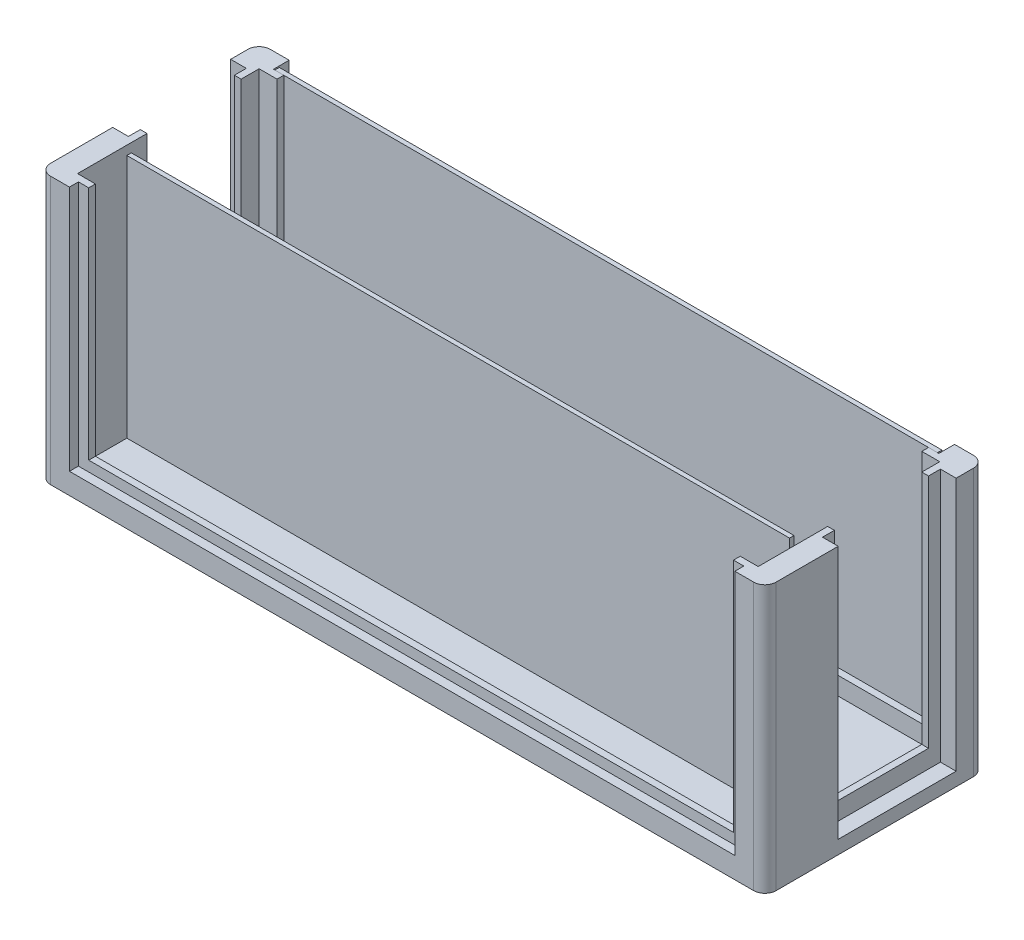
SolidWorks part; units mm, degrees
note: The reader was unsure of these and kept them because the rebuilt part matched: shared geometry of "Sketch2<3>", "Sketch3<3>", "Sketch14<2>".
other "Window_Left"
other "Window_Right"
other "Window_Back"
other "Window_Front"
other "Body"
ref_plane "Front Plane" through (0, 0, 0) normal (0, 0, 1) x (1, 0, 0)
ref_plane "Top Plane" through (0, 0, 0) normal (0, 1, 0) x (1, 0, 0)
ref_plane "Right Plane" through (0, 0, 0) normal (1, 0, 0) x (0, 0, -1)
sketch "Sketch1" plane through (0, 0, 0) normal (0, 0, 1) x (1, 0, 0)
  line L1 (0, 0) -> (157.8, 0)
  line L2 (0, 0) -> (0, 59.6)
  line L3 (0, 59.6) -> (157.8, 59.6)
  line L4 (157.8, 0) -> (157.8, 59.6)
  dimension "D1" = 59.6
  dimension "D2" = 157.8
extrude "Boss-Extrude1" add sketch "Sketch1" along normal blind 35 contours L3 L4 L1 L2
shell "Shell1" thickness 3
sketch "Sketch2" plane through (0, 0, 35) normal (0, 0, 1) x (1, 0, 0)
  line L0 (0, 59.6) -> (157.8, 59.6) construction
  line L1 (5, 59.6) -> (152.8, 59.6)
  line L2 (5, 59.6) -> (5, 5)
  line L3 (5, 5) -> (152.8, 5)
  line L4 (152.8, 59.6) -> (152.8, 5)
  line L5 (0, 0) -> (0, 59.6) construction
  line L6 (157.8, 0) -> (157.8, 59.6) construction
  line L7 (0, 0) -> (157.8, 0) construction
  line L8 (7, 57.6) -> (7, 7)
  line L9 (7, 7) -> (150.8, 7)
  line L10 (150.8, 57.6) -> (150.8, 7)
  line L11 (7, 57.6) -> (150.8, 57.6)
  line L13 (7, 57.6) -> (150.8, 57.6)
  line L14 (7, 57.6) -> (7, 59.6)
  line L15 (7, 59.6) -> (150.8, 59.6)
  line L16 (150.8, 57.6) -> (150.8, 59.6)
  dimension "D1" = 5
  dimension "D2" = 5
  dimension "D3" = 5
  dimension "D4" = 2
extrude "Cut-Extrude1" cut sketch "Sketch2" against normal through all contours L11 L8 L9 L10 | L11 L16 L1 L14
extrude "Cut-Extrude2" cut sketch "Sketch2<3>" against normal blind 1.5 contours L3 L4 L1 L2
sketch "Sketch2<3>" plane through (0, 0, 35) normal (0, 0, 1) x (1, 0, 0) same geometry as "Sketch2"
ref_plane "Plane1" through (0, 0, 17.5) normal (0, 0, 1) x (1, 0, 0)
mirror "Mirror1" about plane through (0, 0, 17.5) normal (0, 0, 1) of "Cut-Extrude2"
sketch "Sketch3" plane through (157.8, 0, 0) normal (1, 0, 0) x (0, 0, -1)
  line L0 (-35, 59.6) -> (0, 59.6) construction
  line L1 (-30, 59.6) -> (-5, 59.6)
  line L2 (-30, 59.6) -> (-30, 5)
  line L3 (-30, 5) -> (-5, 5)
  line L4 (-5, 59.6) -> (-5, 5)
  line L5 (-35, 0) -> (-35, 59.6) construction
  line L6 (0, 0) -> (0, 59.6) construction
  line L7 (-35, 0) -> (0, 0) construction
  line L9 (-28, 59.6) -> (-7, 59.6)
  line L10 (-28, 59.6) -> (-28, 7)
  line L11 (-28, 7) -> (-7, 7)
  line L12 (-7, 59.6) -> (-7, 7)
  dimension "D1" = 5
  dimension "D2" = 5
  dimension "D3" = 5
  dimension "D4" = 2
  dimension "D5" = 2
  dimension "D6" = 2
ref_plane "Plane2" through (78.9, 0, 0) normal (1, 0, 0) x (0, 0, -1)
extrude "Cut-Extrude3" cut sketch "Sketch3" against normal through all contours L12 L1 L10 L11
extrude "Cut-Extrude4" cut sketch "Sketch3<3>" against normal blind 1.5 contours L1 L4 L3 L2
sketch "Sketch3<3>" plane through (157.8, 0, 0) normal (1, 0, 0) x (0, 0, -1) same geometry as "Sketch3"
mirror "Mirror2" about plane through (78.9, 0, 0) normal (1, 0, 0) of "Cut-Extrude4"
sketch "Sketch4" plane through (0, 0, 33.5) normal (0, 0, 1) x (1, 0, 0)
  line L1 (5, 5) -> (152.8, 5)
  line L2 (5, 5) -> (5, 59.6)
  line L3 (5, 59.6) -> (152.8, 59.6)
  line L4 (152.8, 5) -> (152.8, 59.6)
extrude "Boss-Extrude2" add sketch "Sketch4" along normal blind 1 separate body
mirror "Mirror3" about plane through (0, 0, 17.5) normal (0, 0, 1) of bodies 108
sketch "Sketch5" plane through (156.3, 0, 0) normal (1, 0, 0) x (0, 0, -1)
  line L1 (-30, 5) -> (-5, 5)
  line L2 (-30, 5) -> (-30, 59.6)
  line L3 (-30, 59.6) -> (-5, 59.6)
  line L4 (-5, 5) -> (-5, 59.6)
extrude "Boss-Extrude3" add sketch "Sketch5" along normal blind 1 separate body contours L3 L4 L1 L2
mirror "Mirror4" about plane through (78.9, 0, 0) normal (1, 0, 0) of bodies 110
delete or keep bodies "Body-Delete/Keep 1" type delete bodies bodies 110 111
sketch "Sketch6" plane through (157.8, 0, 0) normal (1, 0, 0) x (0, 0, -1)
  line L0 (-35, 59.6) -> (-30, 59.6) construction
  line L1 (-30.15, 59.6) -> (-4.85, 59.6)
  line L2 (-30.15, 59.6) -> (-30.15, 3)
  line L3 (-30.15, 3) -> (-4.85, 3)
  line L4 (-4.85, 59.6) -> (-4.85, 3)
  line L5 (-35, 0) -> (-35, 59.6) construction
  dimension "D1" = 25.3
  dimension "D2" = 4.85
  dimension "D3" = 56.6
extrude "Cut-Extrude5" cut sketch "Sketch6" against normal blind 1.5
mirror "Mirror5" about plane through (78.9, 0, 0) normal (1, 0, 0) of "Cut-Extrude5"
sketch "Sketch7" plane through (157.8, 0, 0) normal (1, 0, 0) x (0, 0, -1)
  line L1 (-30.65, 59.6) -> (-4.35, 59.6)
  line L2 (-30.65, 59.6) -> (-30.65, 3)
  line L3 (-30.65, 3) -> (-4.35, 3)
  line L4 (-4.35, 59.6) -> (-4.35, 3)
  line L5 (-30.15, 3) -> (-4.85, 3) construction
  line L7 (-30.15, 59.6) -> (-30.15, 3) construction
  line L8 (-4.85, 3) -> (-4.85, 59.6) construction
  dimension "D1" = 0.5
  dimension "D2" = 0.5
extrude "Cut-Extrude6" cut sketch "Sketch7" against normal up to surface (1.5 mm away) up to face at (156.3, 32.3, 17.5)
sketch "Sketch8" plane through (0, 0, 0) normal (-1, 0, 0) x (0, 0, 1)
  line L0 (30.65, 3) -> (4.35, 3) construction
  line L1 (4.35, 59.6) -> (4.35, 3) construction
  line L2 (30.65, 59.6) -> (4.35, 59.6) construction
  line L3 (30.65, 59.6) -> (30.65, 3) construction
  line L4 (30.65, 3) -> (4.35, 3)
  line L5 (4.35, 59.6) -> (4.35, 3)
  line L6 (30.65, 59.6) -> (4.35, 59.6)
  line L7 (30.65, 59.6) -> (30.65, 3)
extrude "Cut-Extrude7" cut sketch "Sketch8" against normal up to surface (1.5 mm away) up to face at (1.5, 32.3, 17.5)
sketch "Sketch9" plane through (0, 0, 0) normal (0, 0, -1) x (-1, 0, 0)
  line L8 (0, 59.6) -> (-5, 59.6)
  line L9 (-5, 59.6) -> (-5, 5)
  line L10 (-5, 5) -> (-152.8, 5)
  line L11 (-152.8, 5) -> (-152.8, 59.6)
  line L12 (-152.8, 59.6) -> (-157.8, 59.6)
  line L13 (-157.8, 59.6) -> (-157.8, 0)
  line L14 (-157.8, 0) -> (0, 0)
  line L15 (0, 0) -> (0, 59.6)
  line L16 (0, 59.6) -> (-5, 59.6)
  line L17 (-5, 59.6) -> (-5, 5)
  line L18 (-5, 5) -> (-152.8, 5)
  line L19 (-152.8, 5) -> (-152.8, 59.6)
  line L20 (-152.8, 59.6) -> (-157.8, 59.6)
  line L21 (-157.8, 59.6) -> (-157.8, 0)
  line L22 (-157.8, 0) -> (0, 0)
  line L23 (0, 0) -> (0, 59.6)
  dimension "D1" = 0
extrude "Boss-Extrude4" add sketch "Sketch9" along normal blind 2
sketch "Sketch10" plane through (0, 0, 35) normal (0, 0, 1) x (1, 0, 0)
  line L8 (152.8, 5) -> (5, 5)
  line L9 (5, 5) -> (5, 59.6)
  line L10 (5, 59.6) -> (0, 59.6)
  line L11 (0, 59.6) -> (0, 0)
  line L12 (0, 0) -> (157.8, 0)
  line L13 (157.8, 0) -> (157.8, 59.6)
  line L14 (157.8, 59.6) -> (152.8, 59.6)
  line L15 (152.8, 59.6) -> (152.8, 5)
  line L16 (152.8, 5) -> (5, 5)
  line L17 (5, 5) -> (5, 59.6)
  line L18 (5, 59.6) -> (0, 59.6)
  line L19 (0, 59.6) -> (0, 0)
  line L20 (0, 0) -> (157.8, 0)
  line L21 (157.8, 0) -> (157.8, 59.6)
  line L22 (157.8, 59.6) -> (152.8, 59.6)
  line L23 (152.8, 59.6) -> (152.8, 5)
  dimension "D1" = 0
extrude "Boss-Extrude5" add sketch "Sketch10" along normal blind 2
sketch "Sketch11" plane through (0, 0, 0) normal (-1, 0, 0) x (0, 0, 1)
  line L8 (30.65, 59.6) -> (30.65, 3)
  line L9 (30.65, 3) -> (4.35, 3)
  line L10 (4.35, 3) -> (4.35, 59.6)
  line L11 (4.35, 59.6) -> (-2, 59.6)
  line L12 (-2, 59.6) -> (-2, 0)
  line L13 (-2, 0) -> (37, 0)
  line L14 (37, 0) -> (37, 59.6)
  line L15 (37, 59.6) -> (30.65, 59.6)
  line L16 (30.65, 59.6) -> (30.65, 3)
  line L17 (30.65, 3) -> (4.35, 3)
  line L18 (4.35, 3) -> (4.35, 59.6)
  line L19 (4.35, 59.6) -> (-2, 59.6)
  line L20 (-2, 59.6) -> (-2, 0)
  line L21 (-2, 0) -> (37, 0)
  line L22 (37, 0) -> (37, 59.6)
  line L23 (37, 59.6) -> (30.65, 59.6)
  dimension "D1" = 0
extrude "Boss-Extrude6" add sketch "Sketch11" along normal blind 2
sketch "Sketch12" plane through (157.8, 0, 0) normal (1, 0, 0) x (0, 0, -1)
  line L8 (2, 59.6) -> (-4.35, 59.6)
  line L9 (-4.35, 59.6) -> (-4.35, 3)
  line L10 (-4.35, 3) -> (-30.65, 3)
  line L11 (-30.65, 3) -> (-30.65, 59.6)
  line L12 (-30.65, 59.6) -> (-37, 59.6)
  line L13 (-37, 59.6) -> (-37, 0)
  line L14 (-37, 0) -> (2, 0)
  line L15 (2, 0) -> (2, 59.6)
  line L16 (2, 59.6) -> (-4.35, 59.6)
  line L17 (-4.35, 59.6) -> (-4.35, 3)
  line L18 (-4.35, 3) -> (-30.65, 3)
  line L19 (-30.65, 3) -> (-30.65, 59.6)
  line L20 (-30.65, 59.6) -> (-37, 59.6)
  line L21 (-37, 59.6) -> (-37, 0)
  line L22 (-37, 0) -> (2, 0)
  line L23 (2, 0) -> (2, 59.6)
  dimension "D1" = 0
extrude "Boss-Extrude7" add sketch "Sketch12" along normal blind 2
sketch "Sketch13" plane through (0, 0, 37) normal (0, 0, 1) x (1, 0, 0)
  line L8 (152.8, 59.6) -> (152.8, 5)
  line L9 (152.8, 5) -> (5, 5)
  line L10 (5, 5) -> (5, 59.6)
  line L11 (5, 59.6) -> (-2, 59.6)
  line L12 (-2, 59.6) -> (-2, 0)
  line L13 (-2, 0) -> (159.8, 0)
  line L14 (159.8, 0) -> (159.8, 59.6)
  line L15 (159.8, 59.6) -> (152.8, 59.6)
  line L16 (152.8, 59.6) -> (152.8, 5)
  line L17 (152.8, 5) -> (5, 5)
  line L18 (5, 5) -> (5, 59.6)
  line L19 (5, 59.6) -> (-2, 59.6)
  line L20 (-2, 59.6) -> (-2, 0)
  line L21 (-2, 0) -> (159.8, 0)
  line L22 (159.8, 0) -> (159.8, 59.6)
  line L23 (159.8, 59.6) -> (152.8, 59.6)
  dimension "D1" = 0
extrude "Boss-Extrude8" add sketch "Sketch13" along normal blind 10
ref_plane "Plane3" through (0, 0, 43.5) normal (0, 0, 1) x (1, 0, 0)
sketch "Sketch14" plane through (0, 0, 43.5) normal (0, 0, 1) x (1, 0, 0)
  line L8 (150.8, 7) -> (7, 7)
  line L9 (7, 7) -> (7, 59.6)
  line L10 (7, 59.6) -> (5, 59.6)
  line L11 (5, 59.6) -> (5, 5)
  line L12 (5, 5) -> (152.8, 5)
  line L13 (152.8, 5) -> (152.8, 59.6)
  line L14 (152.8, 59.6) -> (150.8, 59.6)
  line L15 (150.8, 59.6) -> (150.8, 7)
  line L16 (150.8, 7) -> (7, 7)
  line L17 (7, 7) -> (7, 59.6)
  line L18 (7, 59.6) -> (5, 59.6)
  line L19 (5, 59.6) -> (5, 5)
  line L20 (5, 5) -> (152.8, 5)
  line L21 (152.8, 5) -> (152.8, 59.6)
  line L22 (152.8, 59.6) -> (150.8, 59.6)
  line L23 (150.8, 59.6) -> (150.8, 7)
  dimension "D1" = 0
extrude "Cut-Extrude8" cut sketch "Sketch14" against normal up to vertex
extrude "Boss-Extrude10" add sketch "Sketch14<2>" along normal blind 1.5
sketch "Sketch14<2>" plane through (0, 0, 43.5) normal (0, 0, 1) x (1, 0, 0) same geometry as "Sketch14"
sketch "Sketch15" plane through (0, 0, 32) normal (0, 0, -1) x (-1, 0, 0)
  line L8 (-152.8, 5) -> (-152.8, 59.6)
  line L9 (-152.8, 59.6) -> (-154.8, 59.6)
  line L10 (-154.8, 59.6) -> (-154.8, 3)
  line L11 (-154.8, 3) -> (-3, 3)
  line L12 (-3, 3) -> (-3, 59.6)
  line L13 (-3, 59.6) -> (-5, 59.6)
  line L14 (-5, 59.6) -> (-5, 5)
  line L15 (-5, 5) -> (-152.8, 5)
  line L16 (-152.8, 5) -> (-152.8, 59.6)
  line L17 (-152.8, 59.6) -> (-154.8, 59.6)
  line L18 (-154.8, 59.6) -> (-154.8, 3)
  line L19 (-154.8, 3) -> (-3, 3)
  line L20 (-3, 3) -> (-3, 59.6)
  line L21 (-3, 59.6) -> (-5, 59.6)
  line L22 (-5, 59.6) -> (-5, 5)
  line L23 (-5, 5) -> (-152.8, 5)
  dimension "D1" = 0
extrude "Cut-Extrude9" cut sketch "Sketch15" against normal up to vertex (11.5 mm away) up to point (7, 7, 43.5)
sketch "Sketch16" plane through (0, 0, -2) normal (0, 0, -1) x (-1, 0, 0)
  line L0 (-153.1, 4.7) -> (-4.7, 4.7)
  line L1 (-152.8, 5) -> (-5, 5) construction
  line L2 (-152.8, 5) -> (-152.8, 59.6) construction
  line L3 (-152.8, 59.6) -> (-5, 59.6) construction
  line L4 (-5, 5) -> (-5, 59.6) construction
  line L5 (-4.7, 4.7) -> (-4.7, 59.9)
  line L6 (-153.1, 59.9) -> (-4.7, 59.9)
  line L7 (-153.1, 4.7) -> (-153.1, 59.9)
  dimension "D1" = 0.3
extrude "Cut-Extrude10" cut sketch "Sketch16" against normal up to vertex
sketch "Sketch17" plane through (0, 0, 47) normal (0, 0, 1) x (1, 0, 0)
  line L0 (4.7, 4.7) -> (4.7, 59.9)
  line L1 (5, 5) -> (152.8, 5) construction
  line L2 (5, 5) -> (5, 59.6) construction
  line L3 (5, 59.6) -> (152.8, 59.6) construction
  line L4 (152.8, 5) -> (152.8, 59.6) construction
  line L5 (4.7, 59.9) -> (153.1, 59.9)
  line L6 (153.1, 4.7) -> (153.1, 59.9)
  line L7 (4.7, 4.7) -> (153.1, 4.7)
  dimension "D1" = 0.3
extrude "Cut-Extrude11" cut sketch "Sketch17" against normal up to vertex (2 mm away)
fillet "Fillet1" radius 2.5 4 edges at (-2, 29.8, -2) (159.8, 29.8, -2) (-2, 29.8, 47) (159.8, 29.8, 47)
